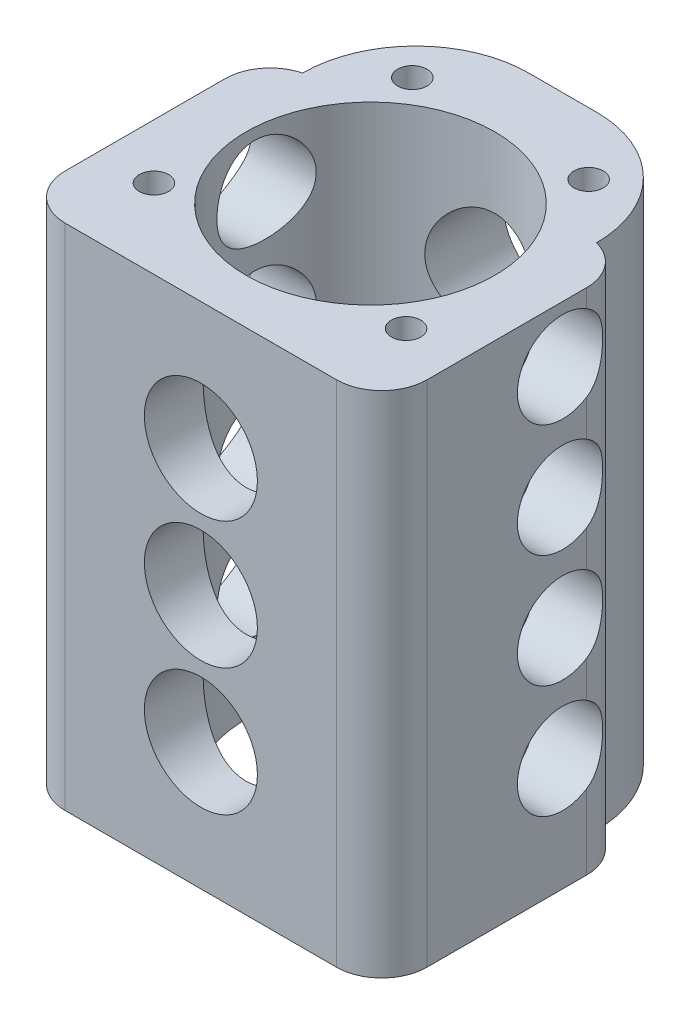
SolidWorks part; units mm, degrees
ref_plane "前视基准面" through (0, 0, 0) normal (0, 0, 1) x (1, 0, 0)
ref_plane "上视基准面" through (0, 0, 0) normal (0, 1, 0) x (1, 0, 0)
ref_plane "右视基准面" through (0, 0, 0) normal (1, 0, 0) x (0, 0, -1)
sketch "草图1" plane through (0, 0, 0) normal (0, 1, 0) x (1, 0, 0)
  line L0 (0, 0) -> (0, 16) construction
  line L1 (0, 16) -> (16, 16)
  line L2 (16, 16) -> (16, -16)
  line L3 (16, -16) -> (-16, -16)
  line L4 (-16, -16) -> (-16, 16)
  line L5 (-16, 16) -> (0, 16)
extrude "凸台-拉伸1" add sketch "草图1" along normal blind 45
sketch "草图2" plane through (0, 45, 0) normal (0, 1, 0) x (1, 0, 0)
  line L0 (0, -16) -> (0, -9) construction
  line L1 (-16, -16) -> (16, -16) construction
  line L2 (0, -9) -> (11.15, -9) construction
  line L3 (0, -9) -> (-11.15, -9) construction
  line L4 (0, -9) -> (0, 10.5) construction
  line L5 (0, 10.5) -> (7.8, 10.5) construction
  line L6 (0, 10.5) -> (-7.8, 10.5) construction
  line L7 (0, -9) -> (0, -1)
  line L8 (-16, 6) -> (-13, 6)
  line L9 (-16, 16) -> (-16, -16) construction
  line L10 (-13, 6) -> (-13, 16)
  line L11 (16, 16) -> (-16, 16) construction
  line L12 (-13, 6) -> (-13.0488, 5.939)
  line L13 (16, -16) -> (16, 16) construction
  line L14 (13, 6) -> (13, 16)
  line L15 (-13, 16) -> (-16, 16)
  line L16 (-16, 16) -> (-16, 6)
  line L17 (13, 16) -> (16, 16)
  line L18 (16, 16) -> (16, 6)
  line L19 (13, 6) -> (16, 6)
  circle A0 centre (-11.15, -9) radius 1.3
  circle A1 centre (11.15, -9) radius 1.3
  circle A2 centre (-7.8, 10.5) radius 1.3
  circle A3 centre (7.8, 10.5) radius 1.3
  circle A4 centre (0, -1) radius 11
extrude "切除-拉伸1" cut sketch "草图2" against normal through all
fillet "圆角1" radius 10 2 edges at (-13, 22.5, -16) (13, 22.5, -16)
fillet "圆角3" radius 4 2 edges at (16, 22.5, 16) (-16, 22.5, 16)
fillet "圆角4" radius 4 2 edges at (16, 22.5, -6) (-16, 22.5, -6)
sketch "草图4" plane through (-16, 0, 0) normal (-1, 0, 0) x (0, 0, 1)
  line L0 (-2.127, 45) -> (-16, 45)
  line L1 (-16, 36) -> (-16, 34)
  line L2 (-16, 0) -> (-16, 45) construction
  line L3 (-16, 0) -> (-16, 10) construction
  line L4 (-16, 11) -> (-16, 9)
  line L5 (-16, 34) -> (-16.0388, 34.0048)
  arc A0 (-16, 11) -> (-16, 9) centre (-16, 10) cw
  arc A1 (-16, 34) -> (-16, 36) centre (-16, 35) ccw
extrude "切除-拉伸2" cut sketch "草图4" against normal through all contours L1 A1 | A0 L4
sketch "草图5" plane through (0, 0, 16) normal (0, 0, 1) x (1, 0, 0)
  line L0 (0, 45) -> (0, 22.5) construction
  line L2 (-12, 45) -> (12, 45) construction
  line L3 (0, 22.5) -> (0, 0) construction
  line L4 (-12, 0) -> (12, 0) construction
  circle A0 centre (0, 22.5) radius 5
  circle A1 centre (0, 33.75) radius 5
  circle A2 centre (0, 11.25) radius 5
extrude "切除-拉伸3" cut sketch "草图5" against normal through all
sketch "草图6" plane through (-16, 0, 0) normal (-1, 0, 0) x (0, 0, 1)
  line L0 (0, 10) -> (0, 20) construction
  line L2 (0, 20) -> (0, 30) construction
  line L3 (0, 0) -> (0, 10) construction
  line L4 (0, 30) -> (0, 40) construction
  circle A0 centre (0, 30) radius 4
  circle A1 centre (0, 20) radius 4
  circle A2 centre (0, 10) radius 4
  circle A3 centre (0, 40) radius 4
extrude "切除-拉伸4" cut sketch "草图6" against normal through all
